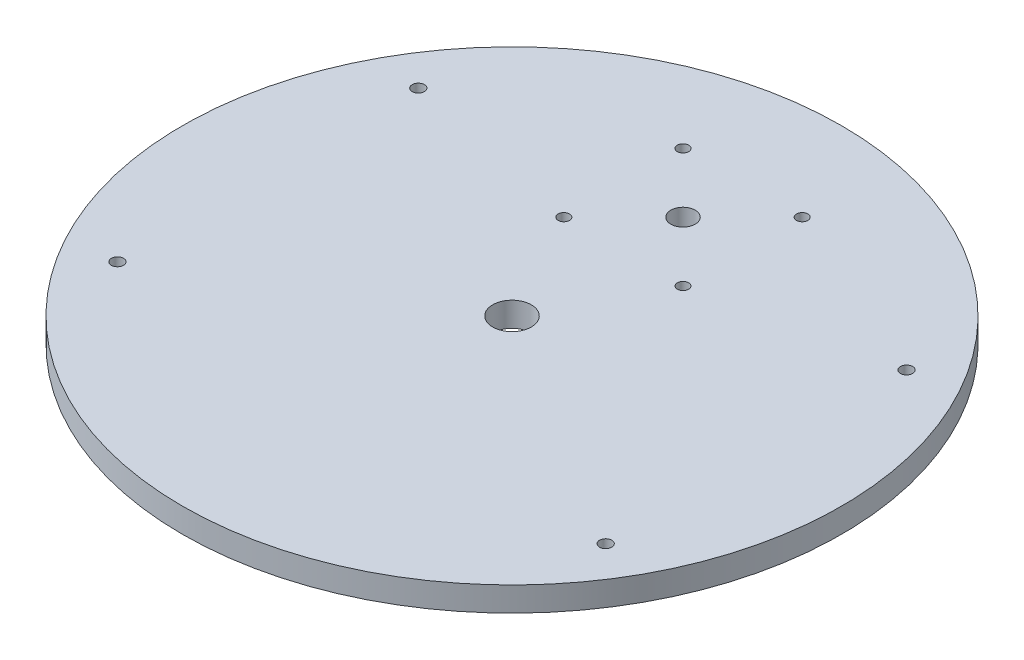
SolidWorks part; units mm, degrees
ref_plane "Front Plane" through (0, 0, 0) normal (0, 0, 1) x (1, 0, 0)
ref_plane "Top Plane" through (0, 0, 0) normal (0, 1, 0) x (1, 0, 0)
ref_plane "Right Plane" through (0, 0, 0) normal (1, 0, 0) x (0, 0, -1)
sketch "Sketch1" plane through (0, 0, 0) normal (0, 1, 0) x (1, 0, 0)
  circle A0 centre (0, 0) radius 85.725
  dimension "D1" = 171.45
extrude "Boss-Extrude1" add sketch "Sketch1" along normal blind 6.35
sketch "Sketch2" plane through (0, 6.35, 0) normal (0, 1, 0) x (1, 0, 0)
  line L0 (-63.5, 39.1325) -> (-63.5, -39.1325) construction
  line L1 (-63.5, -39.1325) -> (63.5, -39.1325) construction
  line L2 (63.5, -39.1325) -> (63.5, 39.1325) construction
  line L3 (63.5, 39.1325) -> (-63.5, 39.1325) construction
  circle A0 centre (-63.5, 39.1325) radius 1.5875
  circle A1 centre (63.5, 39.1325) radius 1.5875
  circle A2 centre (-63.5, -39.1325) radius 1.5875
  circle A3 centre (63.5, -39.1325) radius 1.5875
  dimension "D1" = 3.175
  dimension "D2" = 3.175
  dimension "D3" = 127
  dimension "D4" = 3.175
  dimension "D5" = 3.175
  dimension "D6" = 78.265
  dimension "D8" = 39.1325
  dimension "D9" = 63.5
extrude "Cut-Extrude1" cut sketch "Sketch2" against normal up to next
sketch "Sketch3" plane through (0, 6.35, 0) normal (0, 1, 0) x (1, 0, 0)
  line L0 (0, 44.4822) -> (0, 0) construction
  circle A0 centre (0, 44.4822) radius 3.175
  dimension "D1" = 6.35
  dimension "D2" = 44.4822
extrude "Cut-Extrude2" cut sketch "Sketch3" against normal up to next contours A0
ref_axis "Axis1" through (0, 6.35, 0) along (0, -1, 0)
sketch "Sketch5" plane through (0, 6.35, 0) normal (0, 1, 0) x (1, 0, 0)
  line L1 (-15.5004, 59.9825) -> (15.5003, 59.9825) construction
  line L2 (-15.5004, 59.9825) -> (-15.5003, 28.9818) construction
  line L3 (-15.5003, 28.9818) -> (15.5003, 28.9818) construction
  line L4 (15.5003, 59.9825) -> (15.5003, 28.9818) construction
  line L5 (-15.5004, 59.9825) -> (15.5003, 28.9818) construction
  line L6 (-15.5003, 28.9818) -> (15.5003, 59.9825) construction
  circle A0 centre (0, 44.4822) radius 3.175 construction
  circle A1 centre (0, 44.4822) radius 3.175 construction
  circle A2 centre (-15.5004, 59.9825) radius 1.4732
  circle A3 centre (15.5003, 59.9825) radius 1.4732
  circle A4 centre (-15.5003, 28.9818) radius 1.4732
  circle A5 centre (15.5003, 28.9818) radius 1.4732
  dimension "D3" = 2.9464
  dimension "D4" = 2.9464
  dimension "D5" = 2.9464
  dimension "D6" = 2.9464
  dimension "D1" = 31.0007
  dimension "D2" = 31.0007
extrude "Cut-Extrude3" cut sketch "Sketch5" against normal up to next
sketch "Sketch6" plane through (0, 6.35, 0) normal (0, 1, 0) x (1, 0, 0)
  circle A0 centre (0, 0) radius 5.0165
  dimension "D1" = 10.033
extrude "center_hole" cut sketch "Sketch6" against normal up to next
